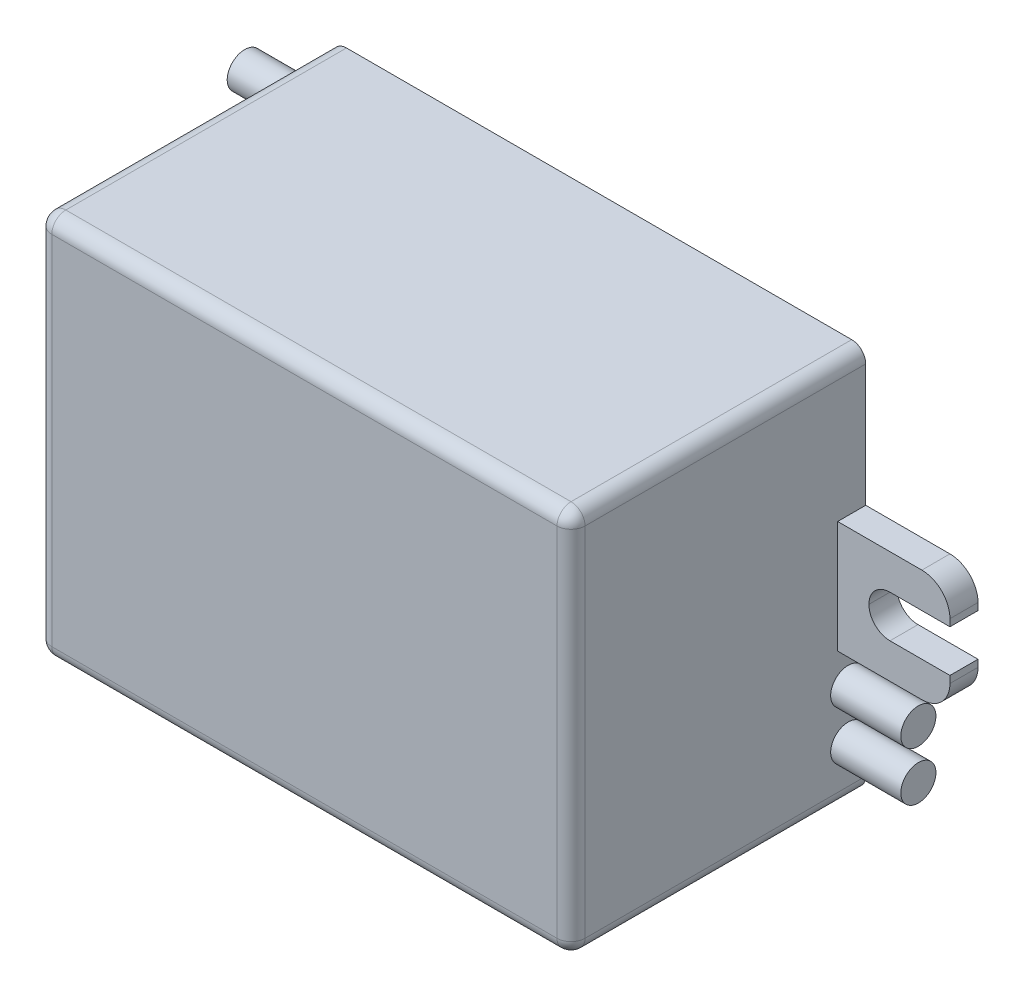
SolidWorks part; units mm, degrees
ref_plane "Front Plane" through (0, 0, 0) normal (0, 0, 1) x (1, 0, 0)
ref_plane "Top Plane" through (0, 0, 0) normal (0, 1, 0) x (1, 0, 0)
ref_plane "Right Plane" through (0, 0, 0) normal (1, 0, 0) x (0, 0, -1)
sketch "Sketch1" plane through (0, 0, 0) normal (0, 0, 1) x (1, 0, 0)
  line L1 (-19, 13.7222) -> (19, 13.7222)
  line L2 (-19, 13.7222) -> (-19, -13.7222)
  line L3 (-19, -13.7222) -> (19, -13.7222)
  line L4 (19, 13.7222) -> (19, -13.7222)
  dimension "D1" = 38
extrude "Boss-Extrude1" add sketch "Sketch1" along normal blind 21
sketch "Sketch2" plane through (0, 0, 0) normal (0, 0, 1) x (1, 0, 0)
  line L0 (-19, 4) -> (-19, -4)
  line L1 (-19, 13.7222) -> (-19, -13.7222) construction
  line L2 (-19, 4) -> (-27, 4)
  line L3 (-27, 4) -> (-27, -4)
  line L4 (-27, -4) -> (-19, -4)
  dimension "D1" = 8
extrude "Boss-Extrude2" add sketch "Sketch2" along normal blind 2
sketch "Sketch3" plane through (0, 0, 2) normal (0, 0, 1) x (1, 0, 0)
  line L1 (-27, 4) -> (-27, -4) construction
  line L2 (-27, 1.5) -> (-21.2259, 1.5)
  line L3 (-21.2259, 1.5) -> (-21.2259, -1.5)
  line L4 (-21.2259, -1.5) -> (-27, -1.5)
  line L5 (-27, -1.5) -> (-27, 1.5)
extrude "Cut-Extrude1" cut sketch "Sketch3" against normal blind 2
fillet "Fillet1" radius 2 2 edges at (-27, -4, 1) (-27, 4, 1)
fillet "Fillet2" radius 1.5 2 edges at (-21.2259, 1.5, 1) (-21.2259, -1.5, 1)
mirror "Mirror1" about plane through (0, 0, 0) normal (1, 0, 0) of "Fillet2", "Cut-Extrude1", "Boss-Extrude2", "Fillet1"
sketch "Sketch5" plane through (-19, 0, 0) normal (-1, 0, 0) x (0, 0, 1)
  line L0 (21, 13.7222) -> (0, 13.7222) construction
  circle A0 centre (1.25, 10) radius 1.25
  circle A1 centre (1.25, 6.5) radius 1.25
  point P0 (10.5, 13.7222)
extrude "Boss-Extrude3" add sketch "Sketch5" along normal blind 5
sketch "Sketch6" plane through (19, 0, 0) normal (1, 0, 0) x (0, 0, -1)
  line L0 (-2, -4) -> (0, -4) construction
  circle A0 centre (-1.25, -6.5) radius 1.25
  circle A1 centre (-1.25, -10) radius 1.25
  point P0 (-1, -4)
  point P7 (-1.25, -6.5)
  point P8 (-1.25, -6.5)
extrude "Boss-Extrude4" add sketch "Sketch6" along normal blind 5
fillet "Fillet5" radius 1 8 edges at (19, 13.7222, 10.5) (19, -13.7222, 10.5) (-19, -13.7222, 10.5) (-19, 13.7222, 10.5) (19, 0, 21) (0, -13.7222, 21) (-19, 0, 21) (0, 13.7222, 21)
